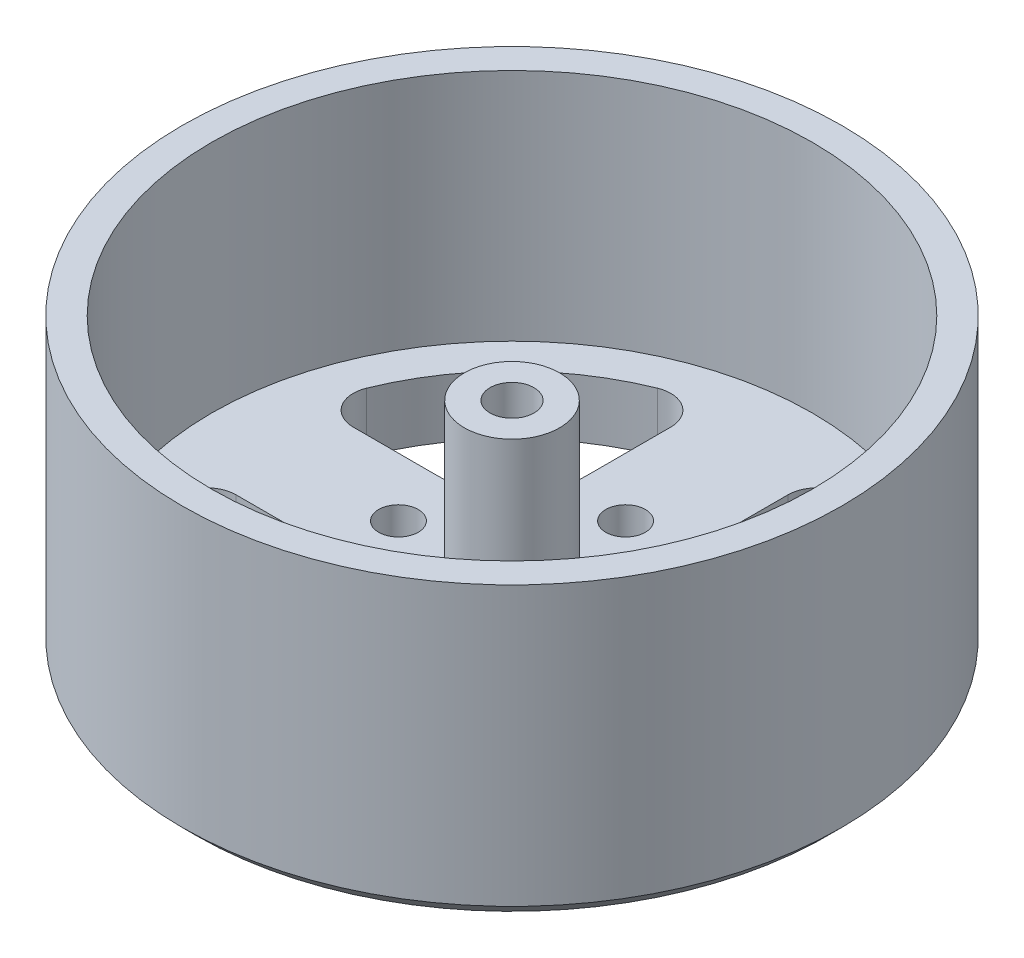
SolidWorks part; units mm, degrees
material "三聚氰胺甲醛树脂"
ref_plane "前视基准面" through (0, 0, 0) normal (0, 0, 1) x (1, 0, 0)
ref_plane "上视基准面" through (0, 0, 0) normal (0, 1, 0) x (1, 0, 0)
ref_plane "右视基准面" through (0, 0, 0) normal (1, 0, 0) x (0, 0, -1)
sketch "草图1" plane through (0, 0, 0) normal (0, 1, 0) x (1, 0, 0)
  line L0 (-17.5499, 4) -> (-4, 4)
  line L1 (-4, 4) -> (-4, 17.5499)
  line L2 (4, 17.5499) -> (4, 4)
  line L3 (4, 4) -> (17.5499, 4)
  line L4 (17.5499, -4) -> (4, -4)
  line L5 (4, -4) -> (4, -17.5499)
  line L6 (-4, -17.5499) -> (-4, -4)
  line L7 (-4, -4) -> (-17.5499, -4)
  circle A0 centre (0, 0) radius 1.5
  circle A1 centre (0, 0) radius 20.5
  circle A2 centre (0, 0) radius 22.5
  circle A3 centre (0, 0) radius 3.25
  circle A4 centre (-7.75, 0) radius 1.35
  circle A5 centre (0, 7.75) radius 1.35
  circle A6 centre (7.75, 0) radius 1.35
  circle A7 centre (0, -7.75) radius 1.35
  arc A8 (-4, 17.5499) -> (-17.5499, 4) centre (0, 0) ccw
  arc A9 (17.5499, 4) -> (4, 17.5499) centre (0, 0) ccw
  arc A10 (-17.5499, -4) -> (-4, -17.5499) centre (0, 0) ccw
  arc A11 (4, -17.5499) -> (17.5499, -4) centre (0, 0) ccw
  point P17 (0, 0)
  point P31 (0, 0)
  dimension "D1" = 6.5
  dimension "D2" = 3
  dimension "D3" = 41
  dimension "D4" = 45
  dimension "D5" = 2.7
  dimension "D6" = 7.75
  dimension "D8" = 36
  dimension "D10" = 8
  dimension "D7" = 4
  dimension "D9" = 4
extrude "凸台-拉伸1" add sketch "草图1" along normal blind 4 contours A1 A11 L5 L4 A10 L7 L6 A9 L3 L2 A8 L1 L0 A7 A6 A5 A4 A3 region at (-19.9202, 0, 0)
extrude "凸台-拉伸2" add sketch "草图1<3>" along normal blind 15 contours A3 A0 region at (-3.1581, 0, 0)
sketch "草图1<3>" plane through (0, 0, 0) normal (0, 1, 0) x (1, 0, 0) same geometry as "草图1"
extrude "凸台-拉伸3" add sketch "草图1<4>" along normal blind 20 contours A2 A1 region at (-21.8636, 0, 0)
sketch "草图1<4>" plane through (0, 0, 0) normal (0, 1, 0) x (1, 0, 0) same geometry as "草图1"
fillet "圆角1" radius 5 4 edges at (-4, 2, 4) (4, 2, 4) (4, 2, -4) (-4, 2, -4)
fillet "圆角2" radius 2 8 edges at (4, 2, 17.5499) (17.5499, 2, 4) (17.5499, 2, -4) (4, 2, -17.5499) (-4, 2, 17.5499) (-17.5499, 2, 4) (-4, 2, -17.5499) (-17.5499, 2, -4)
chamfer "倒角1" distance 1 angle 45 1 edges at (0, 0, 22.5)
